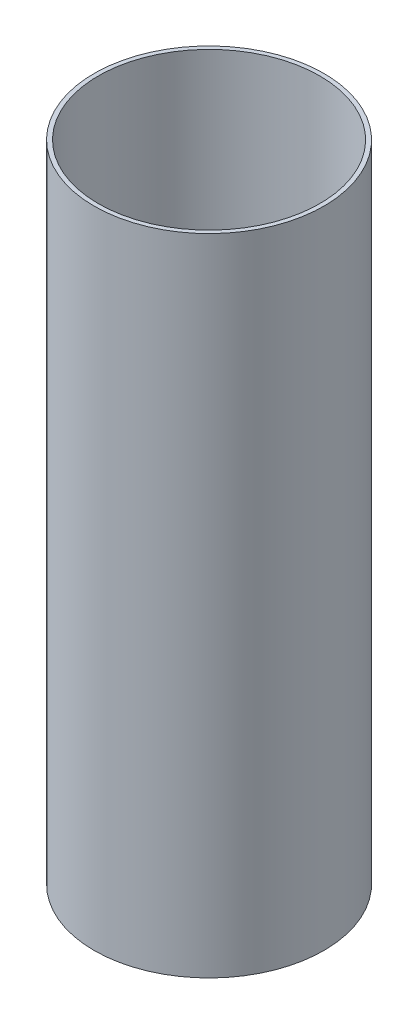
SolidWorks part; units mm, degrees
ref_plane "Front Plane" through (0, 0, 0) normal (0, 0, 1) x (1, 0, 0)
ref_plane "Top Plane" through (0, 0, 0) normal (0, 1, 0) x (1, 0, 0)
ref_plane "Right Plane" through (0, 0, 0) normal (1, 0, 0) x (0, 0, -1)
sketch "Sketch1" plane through (0, 0, 0) normal (0, 1, 0) x (1, 0, 0)
  circle A0 centre (0, 0) radius 41
  circle A1 centre (0, 0) radius 39.5
  dimension "D1" = 79
  dimension "D2" = 82
extrude "Boss-Extrude1" add sketch "Sketch1" along normal blind 230
